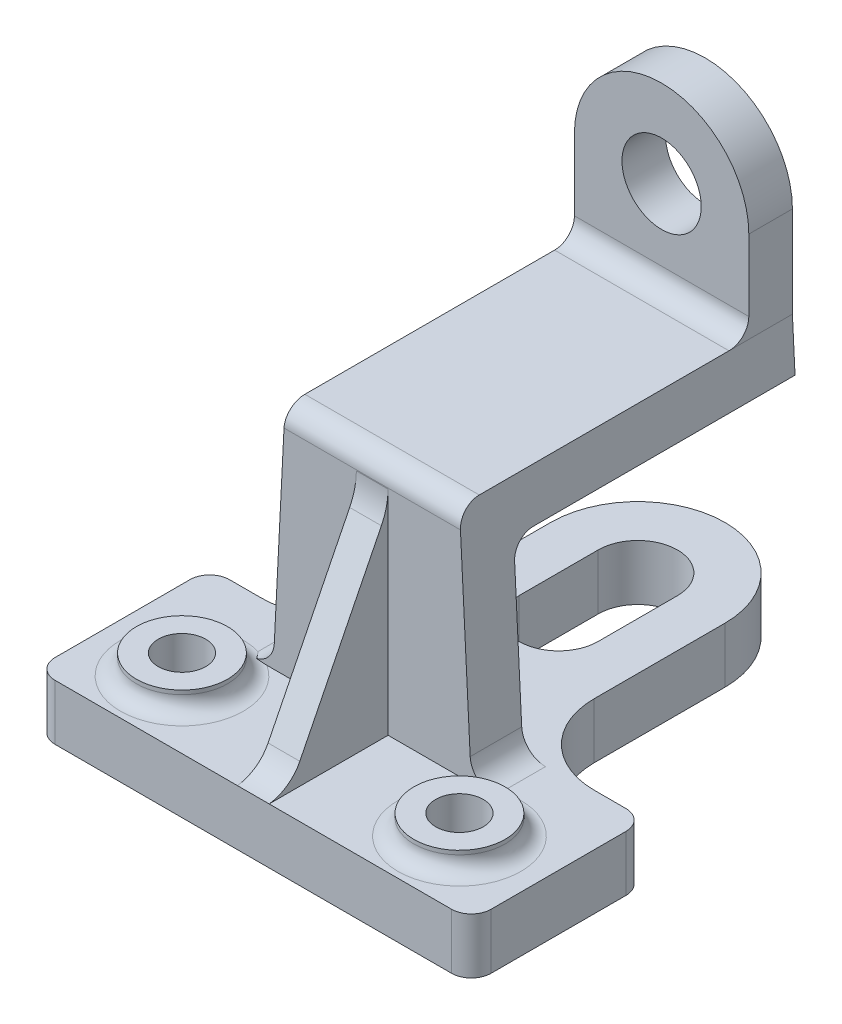
SolidWorks part; units mm, degrees
note: The reader was unsure of these and kept them because the rebuilt part matched: shared geometry of "Sketch1<3>".
material "1060 Alloy"
ref_plane "Front Plane" through (0, 0, 0) normal (0, 0, 1) x (1, 0, 0)
ref_plane "Top Plane" through (0, 0, 0) normal (0, 1, 0) x (1, 0, 0)
ref_plane "Right Plane" through (0, 0, 0) normal (1, 0, 0) x (0, 0, -1)
sketch "Sketch1" plane through (0, 0, 0) normal (0, 1, 0) x (1, 0, 0)
  line L0 (-77, 64) -> (-77, 97)
  line L1 (-5, 0) -> (-105, 0)
  line L2 (0, 5) -> (0, 39)
  line L3 (-5, 44) -> (-13, 44)
  line L4 (-110, 5) -> (-110, 39)
  line L5 (-33, 97) -> (-33, 64)
  line L6 (-55, 97) -> (-55, 77) construction
  line L7 (-45, 97) -> (-45, 77)
  line L8 (-65, 97) -> (-65, 77)
  line L9 (-97, 44) -> (-105, 44)
  circle A0 centre (-20, 17) radius 11.5
  circle A1 centre (-90, 17) radius 11.5
  circle A2 centre (-90, 17) radius 6
  circle A3 centre (-20, 17) radius 6
  arc A4 (-105, 0) -> (-110, 5) centre (-105, 5) cw
  arc A5 (-5, 0) -> (0, 5) centre (-5, 5) ccw
  arc A6 (0, 39) -> (-5, 44) centre (-5, 39) ccw
  arc A7 (-105, 44) -> (-110, 39) centre (-105, 39) ccw
  arc A8 (-77, 97) -> (-33, 97) centre (-55, 97) cw
  arc A9 (-45, 97) -> (-65, 97) centre (-55, 97) ccw
  arc A10 (-65, 77) -> (-45, 77) centre (-55, 77) ccw
  arc A11 (-33, 64) -> (-13, 44) centre (-13, 64) ccw
  arc A12 (-77, 64) -> (-97, 44) centre (-97, 64) cw
  point P12 (-55, 0)
  point P15 (-110, 0)
  point P18 (0, 0)
  point P21 (0, 44)
  point P27 (-55, 87)
  point P30 (-55, 119)
  point P40 (-77, 44)
  dimension "D4" = 23
  dimension "D5" = 12
  dimension "D8" = 5
  dimension "D10" = 22
  dimension "D12" = 10
  dimension "D13" = 20
  dimension "D1" = 110
  dimension "D2" = 44
  dimension "D3" = 17
  dimension "D6" = 70
  dimension "D7" = 35
  dimension "D9" = 80
  dimension "D11" = 20
extrude "Boss-Extrude1" add sketch "Sketch1" along normal blind 14 contours A8 L0 L9 A7 L4 A4 L1 A5 L2 A6 L3 L5 A10 L8 A9 L7 A1 A0
extrude "Boss-Extrude2" add sketch "Sketch1<3>" along normal blind 19 contours A1 A2 | A0 A3
sketch "Sketch1<3>" plane through (0, 0, 0) normal (0, 1, 0) x (1, 0, 0) same geometry as "Sketch1"
sketch "Sketch2" plane through (0, 14, 0) normal (0, 1, 0) x (1, 0, 0)
  line L0 (-5, 0) -> (-105, 0) construction
  line L1 (-80, 43) -> (-30, 43)
  line L2 (-80, 43) -> (-80, 30)
  line L3 (-80, 30) -> (-30, 30)
  line L4 (-30, 43) -> (-30, 30)
  point P4 (-55, 30)
  point P7 (-55, 0)
  dimension "D1" = 50
  dimension "D2" = 13
  dimension "D3" = 30
ref_plane "Plane1" through (0, 73, 0) normal (0, 1, 0) x (1, 0, 0)
sketch "Sketch3" plane through (0, 73, 0) normal (0, 1, 0) x (1, 0, 0)
  line L0 (-80, 43) -> (-30, 43) construction
  line L1 (-77, 43) -> (-33, 43)
  line L2 (-77, 43) -> (-77, 30)
  line L3 (-77, 30) -> (-33, 30)
  line L4 (-33, 43) -> (-33, 30)
  line L5 (-80, 30) -> (-30, 30) construction
  point P8 (-55, 43)
  point P9 (-55, 43)
  dimension "D1" = 44
loft "Loft1" add profiles "Sketch3", "Sketch2"
ref_plane "Plane2" through (-55, 0, 0) normal (1, 0, 0) x (0, 0, -1)
sketch "Sketch4" plane through (-55, 0, 0) normal (1, 0, 0) x (0, 0, -1)
  line L0 (30, 64) -> (5, 14)
  line L1 (30, 73) -> (30, 14) construction
  line L2 (5, 14) -> (39, 14) construction
  line L3 (5, 14) -> (30, 14)
  line L4 (43, 14) -> (30, 14) construction
  line L5 (43, 14) -> (30, 14) construction
  line L6 (30, 14) -> (30, 64)
  dimension "D1" = 50
  dimension "D2" = 25
extrude "Boss-Extrude3" add sketch "Sketch4" along normal mid plane 8
ref_plane "Plane3" through (0, 0, -114) normal (0, 0, 1) x (1, 0, 0)
sketch "Sketch6" plane through (0, 0, -114) normal (0, 0, 1) x (1, 0, 0)
  line L0 (-77, 73) -> (-77.661, 60)
  line L1 (-77, 73) -> (-80, 14) construction
  line L2 (-77.661, 60) -> (-32.339, 60)
  line L3 (-33, 73) -> (-30, 14) construction
  line L4 (-32.339, 60) -> (-33, 73)
  line L5 (-33, 73) -> (-77, 73)
  dimension "D1" = 13
sketch "Sketch7" plane through (0, 0, -43) normal (0, 0, -1) x (-1, 0, 0)
  line L0 (77, 73) -> (77.661, 60) construction
  line L1 (33, 73) -> (77, 73) construction
  line L2 (32.339, 60) -> (33, 73) construction
  line L3 (77.661, 60) -> (32.339, 60) construction
  line L4 (77, 73) -> (77.661, 60)
  line L5 (33, 73) -> (77, 73)
  line L6 (32.339, 60) -> (33, 73)
  line L7 (77.661, 60) -> (32.339, 60)
loft "Loft2" add profiles "Sketch7", "Sketch6"
sketch "Sketch8" plane through (0, 0, -114) normal (0, 0, 1) x (1, 0, 0)
  line L0 (-77, 73) -> (-77, 96)
  line L1 (-33, 96) -> (-33, 73)
  line L2 (-5, 0) -> (-105, 0) construction
  line L3 (-77, 73) -> (-33, 73)
  arc A0 (-77, 96) -> (-33, 96) centre (-55, 96) cw
  circle A1 centre (-55, 96) radius 10
  dimension "D3" = 20
  dimension "D1" = 96
extrude "Boss-Extrude4" add sketch "Sketch8" along normal blind 11
fillet "Fillet1" radius 10 1 edges at (-55, 14, -5)
fillet "Fillet2" radius 16 1 edges at (-55, 64, -30)
fillet "Fillet10" radius 5 10 edges at (-55, 73, -103)
fillet "Fillet8" radius 4 2 edges at (-90, 14, -5.5) (-20, 14, -5.5)
fillet "Fillet9" radius 6 2 edges
